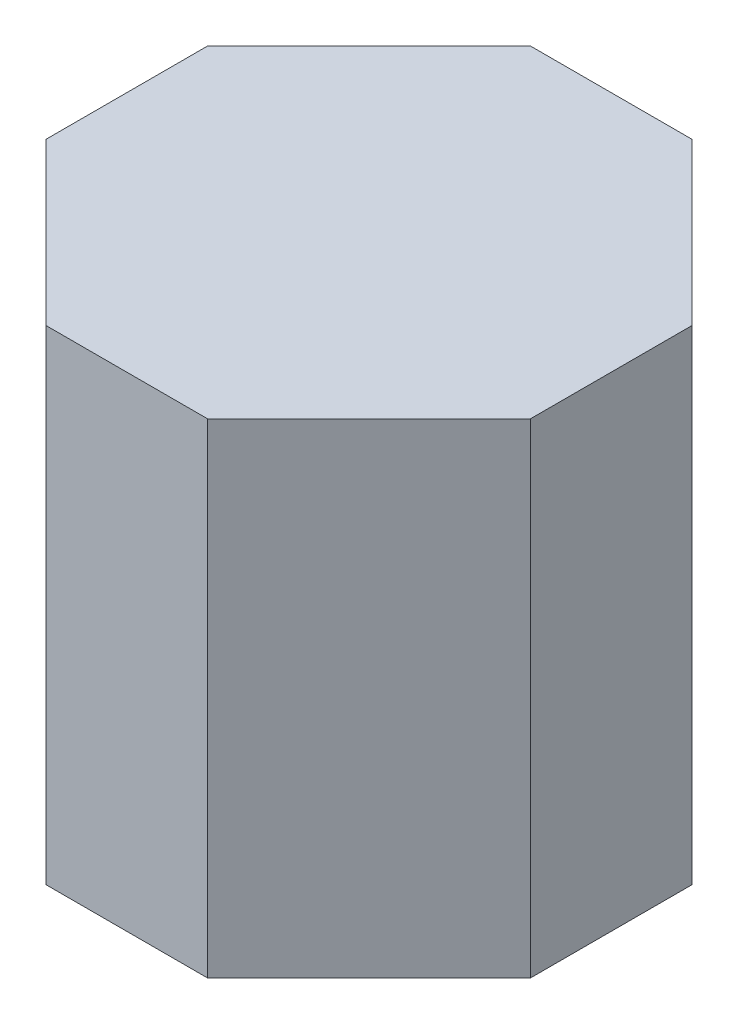
SolidWorks part; units mm, degrees
material "Acier non allié"
ref_plane "Plan de face" through (0, 0, 0) normal (0, 0, 1) x (1, 0, 0)
ref_plane "Plan de dessus" through (0, 0, 0) normal (0, 1, 0) x (1, 0, 0)
ref_plane "Plan de droite" through (0, 0, 0) normal (1, 0, 0) x (0, 0, -1)
sketch "Esquisse1" plane through (0, 0, 0) normal (0, 0, 1) x (1, 0, 0)
  line L0 (15, -15) -> (-15, 15) construction
  line L1 (-15, 15) -> (15, 15)
  line L2 (-15, 15) -> (-15, -15)
  line L3 (-15, -15) -> (15, -15)
  line L4 (15, 15) -> (15, -15)
  line L5 (-15, -15) -> (15, 15) construction
  dimension "D1" = 30
  dimension "D2" = 30
extrude "Boss.-Extru.1" add sketch "Esquisse1" along normal blind 30
sketch "Esquisse3" plane through (0, 15, 0) normal (0, 1, 0) x (1, 0, 0)
  line L0 (-15, -20) -> (-5, -30)
  line L1 (-15, -30) -> (-15, 0) construction
  line L2 (15, -30) -> (-15, -30) construction
  line L3 (-15, -20) -> (-15, -30)
  line L4 (-15, -30) -> (-5, -30)
  line L5 (15, 0) -> (-15, -30) construction
  line L6 (-15, 0) -> (15, -30) construction
  line L7 (-15, 0) -> (-15, -10)
  line L8 (-5, 0) -> (-15, -10)
  line L9 (-5, 0) -> (-15, 0)
  line L10 (15, 0) -> (5, 0)
  line L11 (15, -10) -> (5, 0)
  line L12 (15, -10) -> (15, 0)
  line L13 (15, -30) -> (15, -20)
  line L14 (5, -30) -> (15, -20)
  line L15 (5, -30) -> (15, -30)
  point P16 (0, -15)
  point P29 (0, -15)
  dimension "D1" = 45
  dimension "D2" = 10
  dimension "D3" = 4
extrude "Enlèv. mat.-Extru.1" cut sketch "Esquisse3" against normal up to next
sketch "Esquisse4" plane through (-17.5, 0, 17.5) normal (-0.7071, 0, 0.7071) x (0.7071, 0, 0.7071)
  line L0 (3.5355, -15) -> (3.5355, 15) construction
  line L1 (3.5355, -15) -> (17.6777, -15) construction
  circle A0 centre (10.6055, -5) radius 3.25
  dimension "D1" = 6.5
  dimension "D2" = 7.07
  dimension "D3" = 10
extrude "Enlèv. mat.-Extru.2" cut sketch "Esquisse4" against normal up to next
sketch "Esquisse6" plane through (0, -15, 0) normal (0, -1, 0) x (1, 0, 0)
  circle A0 centre (0, 15) radius 2.75
  dimension "D1" = 5.5
  dimension "D2" = 5
extrude "Enlèv. mat.-Extru.3" cut sketch "Esquisse6" against normal blind 10 contours A0
